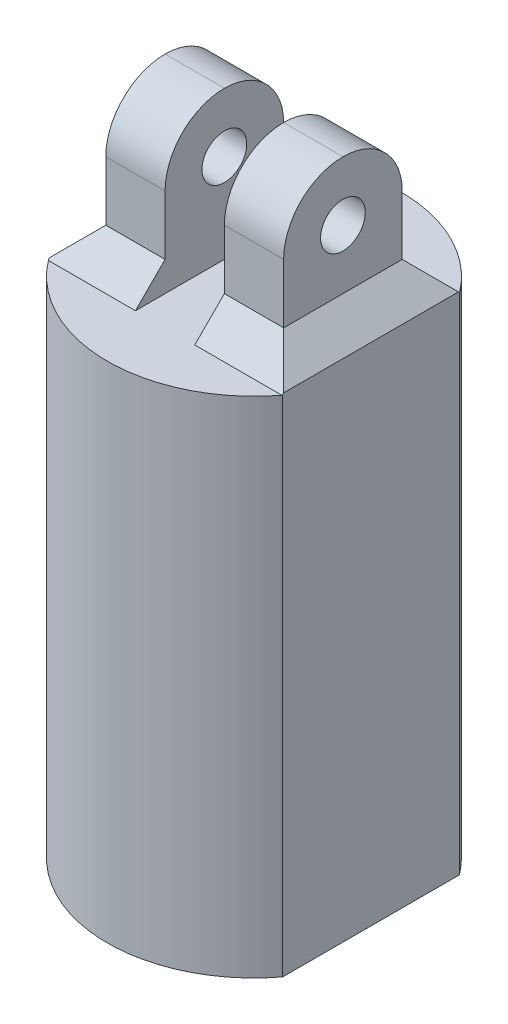
SolidWorks part; units mm, degrees
material "PET"
ref_plane "Front Plane" through (0, 0, 0) normal (0, 0, 1) x (1, 0, 0)
ref_plane "Top Plane" through (0, 0, 0) normal (0, 1, 0) x (1, 0, 0)
ref_plane "Right Plane" through (0, 0, 0) normal (1, 0, 0) x (0, 0, -1)
sketch "Sketch1" plane through (0, 0, 0) normal (0, 1, 0) x (1, 0, 0)
  line L8 (-7.9, 5.9666) -> (-7.9, -5.9666)
  line L11 (7.9, 5.9666) -> (7.9, -5.9666)
  arc A10 (7.9, 5.9666) -> (-7.9, 5.9666) centre (0, 0) ccw
  arc A11 (-7.9, -5.9666) -> (7.9, -5.9666) centre (0, 0) ccw
  point P6 (0, 0)
extrude "Boss-Extrude1" add sketch "Sketch1" along normal blind 34
sketch "Sketch7" plane through (0, 34, 0) normal (0, 1, 0) x (1, 0, 0)
  line L8 (-6, 4) -> (-2, 4)
  line L9 (2, -4) -> (2, 4)
  line L10 (-2, -4) -> (-2, 4)
  line L11 (6, -4) -> (6, 4)
  line L12 (-6, -4) -> (-6, 4)
  line L13 (-6, -4) -> (-2, -4)
  line L14 (2, 4) -> (6, 4)
  line L15 (2, -4) -> (6, -4)
  point P5 (0, 0)
  point P15 (0, 0)
  dimension "D1" = 4
  dimension "D2" = 2
  dimension "D3" = 4
  dimension "D4" = 4
  dimension "D5" = 4
  dimension "D6" = 8
  dimension "D7" = 8
  dimension "D8" = 4
extrude "Boss-Extrude3" add sketch "Sketch7" along normal blind 10
sketch "Sketch9" plane through (6, 0, 0) normal (1, 0, 0) x (0, 0, -1)
  line L0 (-4, 44) -> (4, 44) construction
  circle A0 centre (0, 40) radius 1.51
  dimension "D1" = 4
extrude "Cut-Extrude5" cut sketch "Sketch9" against normal through all
fillet "Fillet2" radius 4 4 edges at (4, 44, 4) (4, 44, -4) (-4, 44, -4) (-4, 44, 4)
sketch "Sketch16" plane through (0, 0, 0) normal (0, -1, 0) x (1, 0, 0)
  circle A0 centre (0, 0) radius 1.5
extrude "Cut-Extrude7" cut sketch "Sketch16" against normal blind 30
chamfer "Chamfer1" distance 2 angle 45 6 edges at (-4, 34, -4) (-6, 34, 0) (-4, 34, 4) (4, 34, -4) (4, 34, 4) (6, 34, 0)
